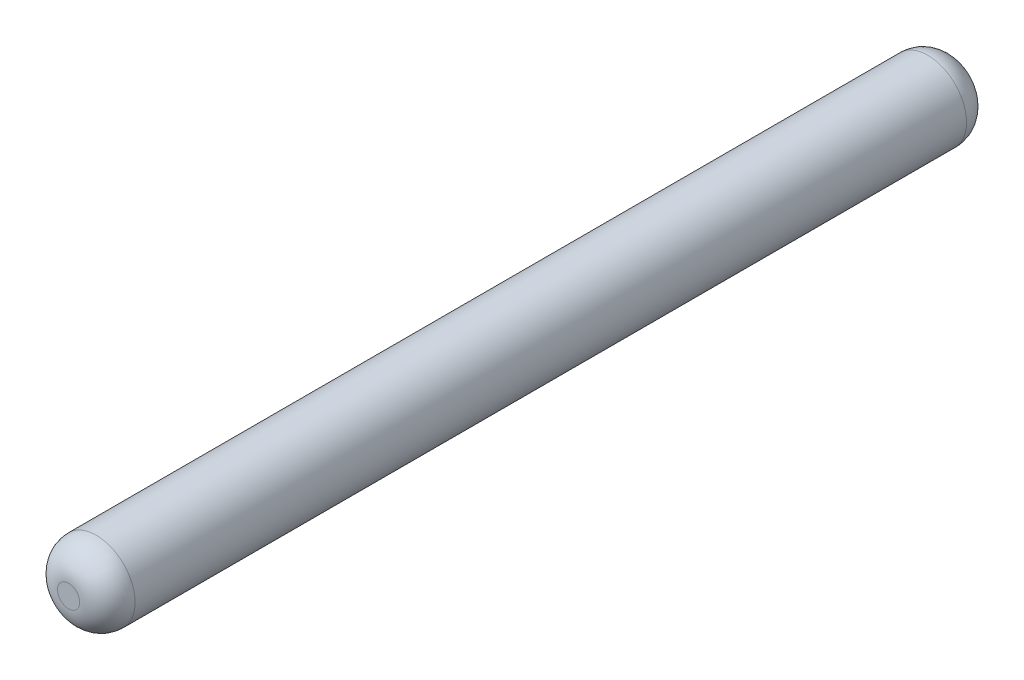
SolidWorks part; units mm, degrees
material "Stainless Steel (ferritic)"
ref_plane "Vorne" through (0, 0, 0) normal (0, 0, 1) x (1, 0, 0)
ref_plane "Oben" through (0, 0, 0) normal (0, 1, 0) x (1, 0, 0)
ref_plane "Rechts" through (0, 0, 0) normal (1, 0, 0) x (0, 0, -1)
ref_axis "Achse1" through (-80.9, 0, 0) along (1, 0, 0)
ref_axis "Achse2" through (0, 0, -80.9) along (0, 0, 1)
sketch "Skizze1" plane through (0, 0, 0) normal (0, 0, 1) x (1, 0, 0)
  circle A0 centre (0, 0) radius 0.525
  dimension "D1" = 1.05
extrude "Aufsatz-Linear austragen1" add sketch "Skizze1" along normal blind 12
ref_plane "Plane1" through (0, 0, 6) normal (0, 0, 1) x (1, 0, 0)
sketch "Sketch1" plane through (0, 0, 12) normal (0, 0, 1) x (1, 0, 0)
  circle A0 centre (0, 0) radius 0.375
  circle A1 centre (0, 0) radius 0.525
  circle A2 centre (0, 0) radius 0.525
  dimension "D2" = 0.75
  dimension "D1" = 0
extrude "Cut-Extrude1" [suppressed] cut sketch "Sketch1" against normal blind 0.5
mirror "Mirror2" [suppressed] about plane through (0, 0, 6) normal (0, 0, 1)
fillet "Fillet2" radius 0.375 2 edges at (0.525, 0, 0) (0.525, 0, 12)
